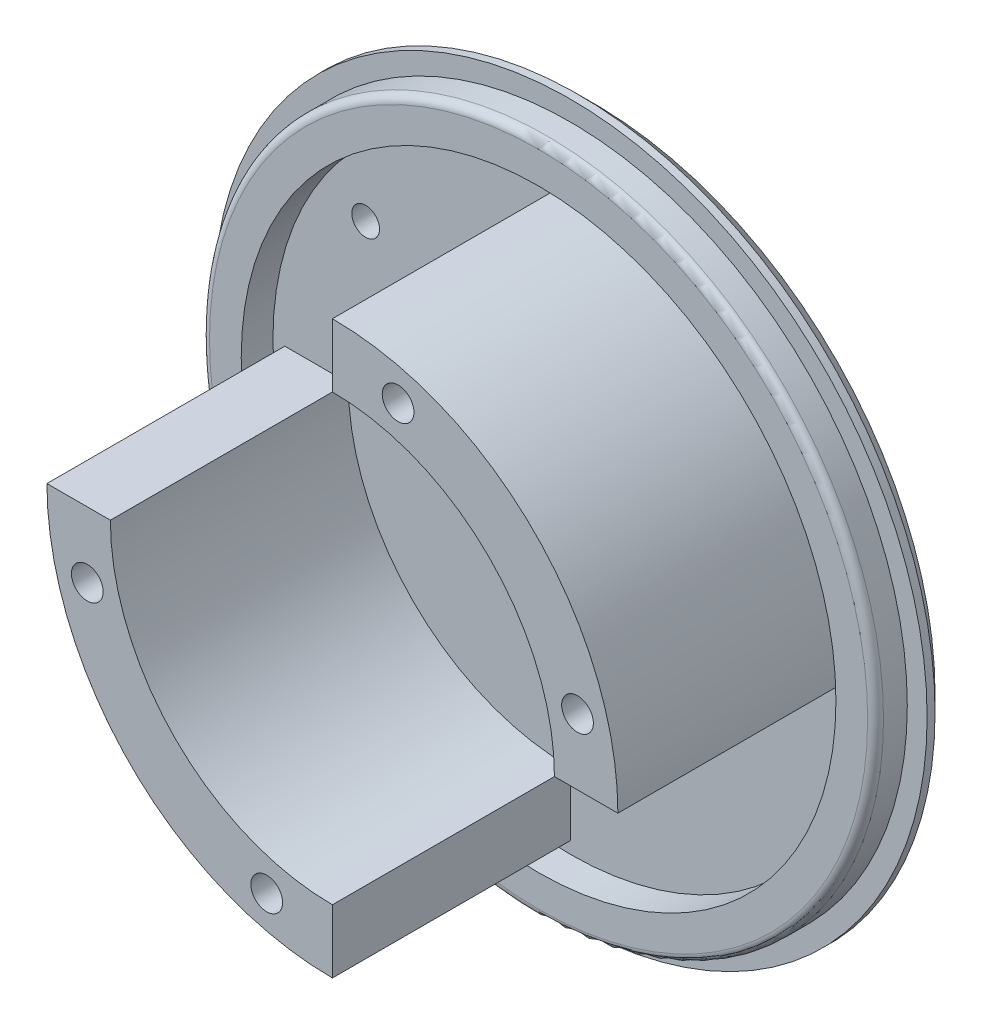
SolidWorks part; units mm, degrees
ref_plane "Front Plane" through (0, 0, 0) normal (0, 0, 1) x (1, 0, 0)
ref_plane "Top Plane" through (0, 0, 0) normal (0, 1, 0) x (1, 0, 0)
ref_plane "Right Plane" through (0, 0, 0) normal (1, 0, 0) x (0, 0, -1)
sketch "Sketch1" plane through (0, 0, 0) normal (0, 0, 1) x (1, 0, 0)
  circle A0 centre (0, 0) radius 45
  dimension "D1" = 90
extrude "Boss-Extrude1" add sketch "Sketch1" along normal blind 3
sketch "Sketch2" plane through (0, 0, 3) normal (0, 0, 1) x (1, 0, 0)
  circle A0 centre (0, 0) radius 42.5
  circle A1 centre (0, 0) radius 37.5
  dimension "D1" = 85
  dimension "D2" = 5
extrude "Boss-Extrude2" add sketch "Sketch2" along normal blind 4
chamfer "Chamfer1" distance 2 angle 45 1 edges at (45, 0, 0)
fillet "Fillet1" radius 1 1 edges at (42.5, 0, 7)
sketch "Sketch3" plane through (0, 0, 3) normal (0, 0, 1) x (1, 0, 0)
  line L0 (-36, 0) -> (-28, 0)
  line L1 (0, -28) -> (0, -36)
  arc A0 (-36, 0) -> (0, -36) centre (0, 0) ccw
  arc A2 (-28, 0) -> (0, -28) centre (0, 0) ccw
  circle A3 centre (0, 0) radius 28 construction
  circle A4 centre (0, 0) radius 36 construction
  dimension "D1" = 72
  dimension "D2" = 8
extrude "Boss-Extrude3" add sketch "Sketch3" along normal blind 30
sketch "Sketch4" plane through (0, 0, 33) normal (0, 0, 1) x (1, 0, 0)
  line L0 (-32, 0) -> (0, 0) construction
  line L1 (0, 0) -> (0, -32) construction
  line L2 (-30.9096, -8.2822) -> (0, 0) construction
  line L3 (0, 0) -> (-8.2822, -30.9096) construction
  circle A1 centre (-30.9096, -8.2822) radius 2
  arc A2 (-32, 0) -> (0, -32) centre (0, 0) ccw
  arc A3 (-32, 0) -> (0, -32) centre (0, 0) ccw construction
  circle A4 centre (-8.2822, -30.9096) radius 2
  dimension "D4" = 4
  dimension "D2" = 15
  dimension "D3" = 15
  dimension "D1" = 4
extrude "Cut-Extrude1" cut sketch "Sketch4" against normal blind 15
pattern_circular "CirPattern1" count 2 every 180 about axis through (0, 0, 3) along (0, 0, 1) of "Boss-Extrude3", "Cut-Extrude1"
sketch "Sketch5" plane through (0, 0, 3) normal (0, 0, 1) x (1, 0, 0)
  line L0 (0, 0) -> (-16.2635, 16.2635) construction
  line L1 (-16.2635, 16.2635) -> (-19.799, 12.7279) construction
  line L2 (-25.8094, 18.7383) -> (-13.7886, 6.7175) construction
  line L3 (0, 0) -> (0, 28) construction
  arc A0 (28, 0) -> (0, 28) centre (0, 0) ccw construction
  arc A1 (28, 0) -> (0, 28) centre (0, 0) ccw construction
  circle A2 centre (-25.8094, 18.7383) radius 1.75
  circle A3 centre (-13.7886, 6.7175) radius 1.75
  dimension "D5" = 3.5
  dimension "D1" = 45
  dimension "D2" = 5
  dimension "D3" = 17
  dimension "D4" = 23
extrude "Cut-Extrude2" cut sketch "Sketch5" against normal through all
